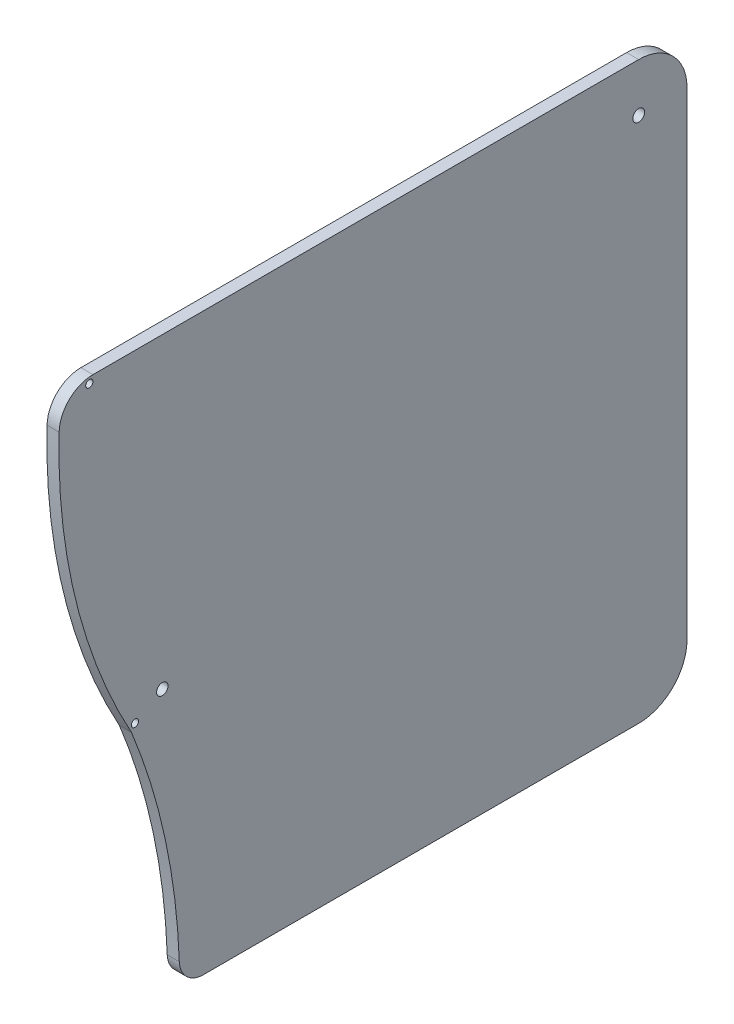
SolidWorks part; units mm, degrees
ref_plane "Front Plane" through (0, 0, 0) normal (0, 0, 1) x (1, 0, 0)
ref_plane "Top Plane" through (0, 0, 0) normal (0, 1, 0) x (1, 0, 0)
ref_plane "Right Plane" through (0, 0, 0) normal (1, 0, 0) x (0, 0, -1)
sketch "Sketch1" plane through (0, 0, 0) normal (1, 0, 0) x (0, 0, -1)
  line L1 (-82.55, 75.565) -> (82.55, 75.565)
  line L2 (-82.55, 75.565) -> (-82.55, -75.565)
  line L3 (-82.55, -75.565) -> (82.55, -75.565)
  line L4 (82.55, 75.565) -> (82.55, -75.565)
  line L9 (69.85, 75.565) -> (69.85, -75.565) construction
  circle A0 centre (69.85, 62.865) radius 1.55
  arc A1 (69.85, -75.565) -> (82.55, -62.865) centre (69.85, -62.865) ccw
  arc A2 (82.55, 62.865) -> (69.85, 75.565) centre (69.85, 62.865) ccw
  point P4 (-82.55, 0)
  point P6 (0, 75.565)
  dimension "D6" = 3.1
  dimension "D1" = 165.1
  dimension "D3" = 151.13
  dimension "D4" = 12.7
  dimension "D5" = 12.7
  dimension "D7" = 12.7
extrude "Boss-Extrude1" add sketch "Sketch1" along normal blind 3.175 contours L9 L1 L2 L3 A0 | L1 L9 A1 L4 region at (0, -0.0191, 0.243)
sketch "Sketch2" plane through (3.175, 0, 0) normal (1, 0, 0) x (0, 0, -1)
  line L0 (-63.5, -75.565) -> (-50.8, -75.565)
  line L2 (-82.55, 62.865) -> (-82.55, -75.565)
  line L3 (-82.55, -75.565) -> (-63.5, -75.565)
  line L5 (-82.55, 75.565) -> (-82.0199, 75.565)
  line L6 (-82.55, 75.565) -> (69.85, 75.565) construction
  line L7 (-82.55, 75.565) -> (-82.55, 62.865)
  line L8 (-63.5, -10.9153) -> (-63.5, -75.565)
  line L9 (82.55, 62.865) -> (82.55, -62.865) construction
  line L11 (-50.8, 75.565) -> (-50.8, -75.565) construction
  line L12 (-82.55, -75.565) -> (69.85, -75.565) construction
  arc A1 (-82.0199, 75.565) -> (-63.5, -10.9153) centre (69.85, 62.865) ccw
  arc A4 (-50.8, -75.565) -> (-63.5, -10.9153) centre (-221.7004, -75.565) ccw
  line M6 (69.85, 75.565) -> (-82.55, 75.565)
  line M7 (-82.55, 75.565) -> (-82.55, -75.565)
  line M8 (-82.55, -75.565) -> (69.85, -75.565)
  dimension "D1" = 146.05
  dimension "D2" = 133.35
extrude "Cut-Extrude1" cut sketch "Sketch2" against normal through all contours A1 M7 M8 | A1 M6 M7 | A4 L8 M8 region at (3.175, -51.1966, 58.4035) region at (3.175, 72.3911, 82.391) region at (3.175, -29.5833, 74.0728)
fillet "Fillet1" radius 8.89 1 edges at (1.5875, 75.565, 82.0199)
sketch "Sketch3" plane through (3.175, 0, 0) normal (1, 0, 0) x (0, 0, -1)
  circle A0 centre (-55.3788, -5.135) radius 1.5
  circle A1 centre (69.85, 62.865) radius 1.55 construction
  point P2 (-47.5237, -17.9414)
  dimension "D1" = 3
  dimension "D2" = 142.5
  dimension "D3" = 68
extrude "Cut-Extrude2" cut sketch "Sketch3" against normal through all
sketch "Sketch4" plane through (3.175, 0, 0) normal (1, 0, 0) x (0, 0, -1)
  line L0 (-73.6094, 72.39) -> (-73.6094, 75.565)
  line L1 (-60.7219, -9.3782) -> (-63.5, -10.9153)
  line L2 (-74.5619, 73.9775) -> (-73.6094, 73.9775) construction
  line L3 (-62.1109, -10.1468) -> (-62.5721, -9.3134) construction
  arc A0 (-82.4963, 66.911) -> (-63.5, -10.9153) centre (69.85, 62.865) ccw construction
  arc A1 (-73.6094, 75.565) -> (-82.4963, 66.911) centre (-73.6094, 66.675) ccw construction
  arc A2 (-82.4963, 66.911) -> (-63.5, -10.9153) centre (69.85, 62.865) ccw
  arc A3 (-73.6094, 75.565) -> (-82.4963, 66.911) centre (-73.6094, 66.675) ccw
  arc A4 (-73.6094, 72.39) -> (-79.3224, 66.8267) centre (-73.6094, 66.675) ccw
  arc A5 (-79.3224, 66.8267) -> (-60.7219, -9.3782) centre (69.85, 62.865) ccw
  circle A6 centre (-74.5619, 73.9775) radius 0.9525
  circle A7 centre (-62.5721, -9.3134) radius 0.9525
  dimension "D2" = 1.905
  dimension "D1" = 3.175
extrude "Cut-Extrude3" cut sketch "Sketch4" against normal through all contours A6 | A7 region at (3.175, 73.9775, 74.5619) region at (3.175, -9.3134, 62.5721)
fillet "Fillet2" radius 6.35 1 edges at (1.5875, -75.565, 50.8)
equation "\"bottomThickness\"= .25in"
equation "\"wallThickness\"= .125in"
equation "\"D1@Boss-Extrude1\"=\"wallThickness\""
